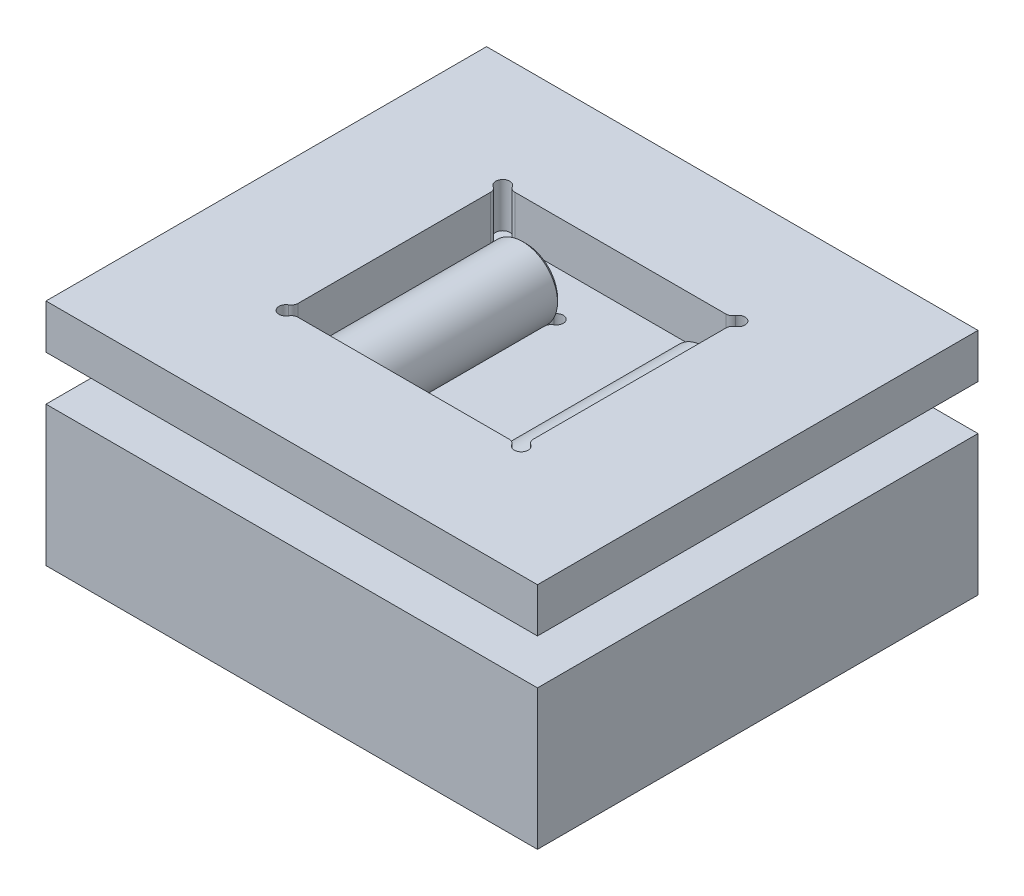
SolidWorks part; units mm, degrees
ref_plane "Front Plane" through (0, 0, 0) normal (0, 0, 1) x (1, 0, 0)
ref_plane "Top Plane" through (0, 0, 0) normal (0, 1, 0) x (1, 0, 0)
ref_plane "Right Plane" through (0, 0, 0) normal (1, 0, 0) x (0, 0, -1)
sketch "Sketch1" plane through (0, 0, 0) normal (0, 0, 1) x (1, 0, 0)
  line L0 (-6.4952, -3.75) -> (6.4952, -3.75) construction
  line L5 (-6.4952, -3.75) -> (0, 0) construction
  line L6 (-6.4952, -3.75) -> (-4.5801, -5.357) construction
  line L11 (-4.5801, -5.357) -> (4.5801, -5.357)
  line L12 (4.5801, -5.357) -> (4.5801, -15.357)
  line L13 (4.5801, -15.357) -> (-4.5801, -15.357)
  line L14 (-4.5801, -15.357) -> (-4.5801, -5.357)
  line L15 (-8.4103, -5.357) -> (-8.4103, -15.357)
  line L16 (-8.4103, -15.357) -> (-17.5705, -15.357)
  line L17 (-17.5705, -15.357) -> (-17.5705, -5.357)
  line L18 (-17.5705, -5.357) -> (-8.4103, -5.357)
  line L19 (0, -5.357) -> (0, -15.357) construction
  line L20 (17.5705, -5.357) -> (8.4103, -5.357)
  line L21 (8.4103, -15.357) -> (17.5705, -15.357)
  line L22 (8.4103, -5.357) -> (8.4103, -15.357)
  line L23 (17.5705, -15.357) -> (17.5705, -5.357)
  line L24 (-8.4103, -2.143) -> (-17.5705, -2.143)
  line L25 (-6.4952, -3.75) -> (-8.4103, -2.143) construction
  line L26 (-17.5705, -2.143) -> (-17.5705, 1.032)
  line L27 (-17.5705, 1.032) -> (-8.4103, 1.032)
  line L28 (-8.4103, 1.032) -> (-8.4103, -2.143)
  line L29 (17.5705, 1.032) -> (8.4103, 1.032)
  line L30 (17.5705, -2.143) -> (17.5705, 1.032)
  line L31 (8.4103, -2.143) -> (17.5705, -2.143)
  line L32 (8.4103, 1.032) -> (8.4103, -2.143)
  circle A1 centre (0, 0) radius 5
  circle A2 centre (6.4952, -3.75) radius 2.5
  circle A3 centre (-6.4952, -3.75) radius 2.5
  point P21 (0, -5)
  dimension "D1" = 10
  dimension "D2" = 5
  dimension "D3" = 30
  dimension "D4" = 40
  dimension "D5" = 10
  dimension "D7" = 3.175
extrude "Boss-Extrude1" add sketch "Sketch1" along normal blind 7.75 contours L14 L13 L12 L11 | L21 L23 L20 L22 | L18 L15 L16 L17 | L28 L24 L26 L27 | L29 L32 L31 L30 region at (0, -10.357, 0) region at (12.9904, -10.357, 0)
sketch "Sketch2" plane through (0, 0, 7.75) normal (0, 0, 1) x (1, 0, 0)
  line L1 (-17.5705, -5.357) -> (17.5705, -5.357)
  line L2 (-17.5705, -5.357) -> (-17.5705, -15.357)
  line L3 (-17.5705, -15.357) -> (17.5705, -15.357)
  line L4 (17.5705, -5.357) -> (17.5705, -15.357)
  line L5 (-17.5705, -2.143) -> (17.5705, -2.143)
  line L6 (-17.5705, -2.143) -> (-17.5705, 1.032)
  line L7 (-17.5705, 1.032) -> (17.5705, 1.032)
  line L8 (17.5705, -2.143) -> (17.5705, 1.032)
extrude "Boss-Extrude2" add sketch "Sketch2" along normal blind 8
sketch "Sketch3" plane through (0, -5.357, 0) normal (0, 1, 0) x (1, 0, 0)
  circle A0 centre (-8.4103, -7.75) radius 0.5
  circle A1 centre (-4.5801, -7.75) radius 0.5
  circle A2 centre (4.5801, -7.75) radius 0.5
  circle A3 centre (8.4103, -7.75) radius 0.5
  dimension "D1" = 1
extrude "Cut-Extrude1" cut sketch "Sketch3" against normal through all
sketch "Sketch4" plane through (0, 1.032, 0) normal (0, 1, 0) x (1, 0, 0)
  circle A0 centre (-8.4103, -7.75) radius 0.5
  circle A1 centre (8.4103, -7.75) radius 0.5
  arc A2 (-5.0801, -7.75) -> (-4.5801, -7.25) centre (-4.5801, -7.75) ccw construction
extrude "Cut-Extrude2" cut sketch "Sketch4" against normal up to surface (3.175 mm away) up to face at (0, -2.143, 5.875)
fillet "Fillet1" radius 0.5 8 edges at (4.5801, -10.357, 7.25) (8.4103, -10.357, 7.25) (7.9103, -10.357, 7.75) (5.0801, -10.357, 7.75) (-4.5801, -10.357, 7.25) (-5.0801, -10.357, 7.75) (-7.9103, -10.357, 7.75) (-8.4103, -10.357, 7.25)
fillet "Fillet2" radius 0.5 4 edges at (8.4103, -0.5555, 7.25) (7.9103, -0.5555, 7.75) (-8.4103, -0.5555, 7.25) (-7.9103, -0.5555, 7.75)
mirror "Mirror1" about plane through (0, 0, 0) normal (0, 0, -1) of bodies 105 112
extrude "Boss-Extrude3" add sketch "Sketch1<3>" along normal mid plane 15 separate body contours A2 | A3 region at (6.4952, -3.75, 0)
sketch "Sketch1<3>" plane through (0, 0, 0) normal (0, 0, 1) x (1, 0, 0) same geometry as "Sketch1"
chamfer "Chamfer1" distance 0.25 angle 45 2 edges at (-3.9952, -3.75, -7.5) (-3.9952, -3.75, 7.5)
chamfer "Chamfer2" distance 0.25 angle 45 2 edges at (8.9952, -3.75, -7.5) (8.9952, -3.75, 7.5)
